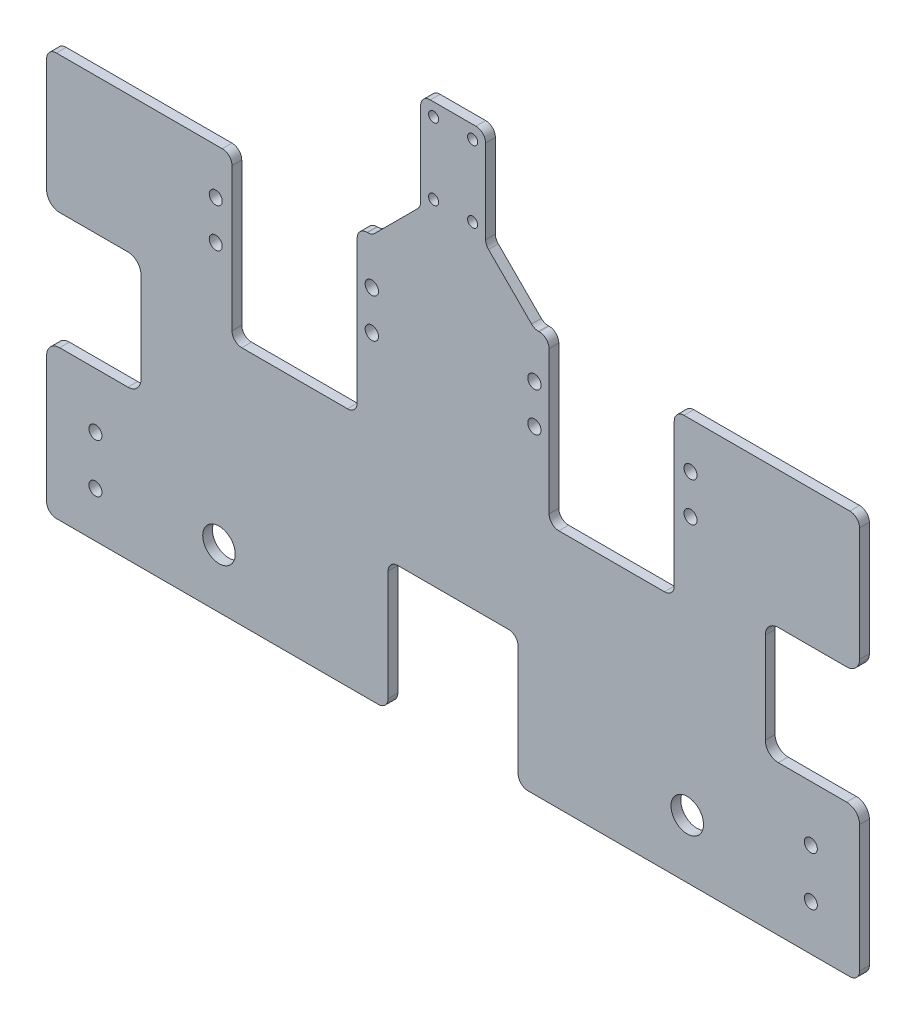
SolidWorks part; units mm, degrees
material "Thornel Mat VMA"
ref_plane "前视基准面" through (0, 0, 0) normal (0, 0, 1) x (1, 0, 0)
ref_plane "上视基准面" through (0, 0, 0) normal (0, 1, 0) x (1, 0, 0)
ref_plane "右视基准面" through (0, 0, 0) normal (1, 0, 0) x (0, 0, -1)
other "Configuration Table"
sketch "草图1" plane through (0, 0, 0) normal (0, 0, 1) x (1, 0, 0)
  line L0 (-32.5, 40) -> (-25, 40)
  line L1 (-25, 40) -> (-10, 55)
  line L2 (-10, 55) -> (-10, 85)
  line L3 (-10, 85) -> (10, 85)
  line L4 (-32.5, 40) -> (-32.5, 0)
  line L5 (-32.5, 0) -> (32.5, 0)
  line L6 (0, 0) -> (0, 50.9699) construction
  line L7 (32.5, 40) -> (32.5, 0)
  line L8 (10, 55) -> (10, 85)
  line L9 (25, 40) -> (10, 55)
  line L10 (32.5, 40) -> (25, 40)
  dimension "D1" = 65
  dimension "D2" = 85
  dimension "D3" = 30
  dimension "D4" = 40
  dimension "D5" = 50
  dimension "D6" = 20
extrude "凸台-拉伸1" add sketch "草图1" along normal blind 3
sketch "草图2" plane through (0, 0, 3) normal (0, 0, 1) x (1, 0, 0)
  line L0 (0, 85) -> (0, 65.679) construction
  line L1 (10, 85) -> (-10, 85) construction
  line L2 (-10, 70) -> (13.1812, 70) construction
  line L3 (-10, 85) -> (-10, 55) construction
  circle A0 centre (-6, 81) radius 1.55
  circle A2 centre (-6, 59) radius 1.55
  circle A3 centre (6, 59) radius 1.55
  circle A4 centre (6, 81) radius 1.55
  dimension "D1" = 4
  dimension "D2" = 4
  dimension "D3" = 3.1
extrude "切除-拉伸1" cut sketch "草图2" against normal through all
sketch "草图3" plane through (0, 0, 3) normal (0, 0, 1) x (1, 0, 0)
  line L0 (32.5, 20) -> (-48.6379, 20) construction
  line L1 (32.5, 0) -> (32.5, 40) construction
  line L2 (0, 0) -> (0, 100.1432) construction
  circle A0 centre (-25, 26) radius 2.05
  circle A2 centre (-25, 14) radius 2.05
  circle A3 centre (25, 14) radius 2.05
  circle A4 centre (25, 26) radius 2.05
  dimension "D1" = 12
  dimension "D2" = 50
  dimension "D3" = 4.1
extrude "切除-拉伸2" cut sketch "草图3" against normal through all
sketch "草图4" plane through (0, 0, 3) normal (0, 0, 1) x (1, 0, 0)
  line L0 (32.5, 0) -> (32.5, 40) construction
  line L1 (32.5, 40) -> (29.5, 40)
  line L2 (32.5, 40) -> (32.5, -0.4765)
  line L3 (32.5, -0.4765) -> (29.5, -0.4765)
  line L4 (29.5, 40) -> (29.5, -0.4765)
  line L5 (0, 85) -> (0, -21.7177) construction
  line L6 (10, 85) -> (-10, 85) construction
  line L7 (-29.5, 40) -> (-29.5, -0.4765)
  line L8 (-32.5, -0.4765) -> (-29.5, -0.4765)
  line L9 (-32.5, 40) -> (-32.5, -0.4765)
  line L10 (-32.5, 40) -> (-29.5, 40)
  dimension "D1" = 3
extrude "切除-拉伸3" cut sketch "草图4" against normal blind 10
sketch "草图5" plane through (0, 0, 3) normal (0, 0, 1) x (1, 0, 0)
  line L0 (0, 0) -> (0, -185.4243) construction
  line L1 (-125, -10) -> (125, -10)
  line L2 (0, 0) -> (0, -84)
  line L3 (-125, -84) -> (125, -84)
  line L4 (125, -10) -> (125, -84)
  line L5 (-125, -10) -> (-125, -84)
  line L6 (-68, -10) -> (-68, 40)
  line L7 (125, -10) -> (68, -10)
  line L8 (125, -10) -> (125, 40)
  line L9 (125, 40) -> (68, 40)
  line L10 (68, -10) -> (68, 40)
  line L11 (-125, 40) -> (-68, 40)
  line L12 (-125, -10) -> (-125, 40)
  line L13 (-125, -10) -> (-68, -10)
  line L14 (-125, -10) -> (-125, -84)
  line L16 (29.5, 40) -> (29.5, 0) construction
  line L17 (-29.5, 0) -> (29.5, 0)
  line L18 (-29.5, 0) -> (-29.5, -10)
  line L19 (-29.5, -10) -> (29.5, -10)
  line L20 (29.5, 0) -> (29.5, -10)
  line M16 (-29.5, 0) -> (29.5, 0)
  dimension "D1" = 250
  dimension "D2" = 50
  dimension "D3" = 68
  dimension "D4" = 74
  dimension "D5" = 10
extrude "凸台-拉伸2" add sketch "草图5" against normal blind 3 contours L10 L1 L8 L9 | L4 L1 L2 L3 | L1 L5 L3 L2 M16 | L12 L1 L6 L11 | L18 L1 L2 M16 | L20 L2 L1 M16 region at (-96.5, 15, 3) region at (-62.5, -47, 3) region at (-14.75, -5, 3) region at (62.5, -47, 3) region at (14.75, -5, 3) region at (96.5, 15, 3)
sketch "草图6" plane through (0, 0, 3) normal (0, 0, 1) x (1, 0, 0)
  line L0 (0, 0) -> (0, -103.0936) construction
  line L1 (-125, -84) -> (125, -84) construction
  line L2 (-20, -84) -> (20, -84)
  line L3 (0, -84) -> (0, -44)
  line L4 (-20, -44) -> (20, -44)
  line L5 (20, -84) -> (20, -44)
  line L6 (-20, -84) -> (-20, -44)
  line M14 (-125, -84) -> (125, -84)
  dimension "D1" = 20
  dimension "D2" = 40
extrude "切除-拉伸4" cut sketch "草图6" against normal blind 4 contours L2 L5 L4 L3 | L6 L3 L4 M14 region at (-10, -64, 3) region at (10, -64, 3)
fillet "圆角1" radius 3 22 edges at (-20, -44, 1.5) (20, -44, 1.5) (20, -84, 1.5) (125, -84, 1.5) (68, 40, 1.5) (68, -10, 1.5) (29.5, -10, 1.5) (29.5, 40, 1.5) (25, 40, 1.5) (10, 55, 1.5) (10, 85, 1.5) (-10, 85, 1.5) (-10, 55, 1.5) (-25, 40, 1.5) (-29.5, 40, 1.5) (-29.5, -10, 1.5) (-68, -10, 1.5) (-68, 40, 1.5) (-125, 40, 1.5) (-125, -84, 1.5) (-20, -84, 1.5) (125, 40, 1.5)
sketch "草图7" plane through (0, 0, 3) normal (0, 0, 1) x (1, 0, 0)
  line L0 (125, -81) -> (125, 37) construction
  line L1 (23, -84) -> (122, -84) construction
  line L2 (0, 0) -> (0, -96.374) construction
  line L3 (122, 40) -> (71, 40) construction
  line L4 (96, -2) -> (127, -2)
  line L5 (96, -2) -> (96, -38)
  line L6 (96, -38) -> (127, -38)
  line L7 (127, -2) -> (127, -38)
  line L8 (-127, -2) -> (-127, -38)
  line L9 (-96, -38) -> (-127, -38)
  line L10 (-96, -2) -> (-96, -38)
  line L11 (-96, -2) -> (-127, -2)
  circle A0 centre (72, -66) radius 5
  circle A1 centre (-72, -66) radius 5
  dimension "D1" = 53
  dimension "D2" = 10
  dimension "D3" = 18
  dimension "D4" = 42
  dimension "D5" = 29
  dimension "D6" = 36
  dimension "D7" = 31
extrude "切除-拉伸5" cut sketch "草图7" against normal blind 4
sketch "草图8" plane through (0, 0, 3) normal (0, 0, 1) x (1, 0, 0)
  line L0 (0, 95.4541) -> (0, -92.5342) construction
  line L1 (122, 40) -> (71, 40) construction
  line L2 (125, -2) -> (125, 37) construction
  circle A0 centre (73, 26) radius 2
  circle A1 centre (73, 14) radius 2
  circle A2 centre (-73, 14) radius 2
  circle A3 centre (-73, 26) radius 2
  dimension "D1" = 4
  dimension "D2" = 4
  dimension "D3" = 12
  dimension "D4" = 14
  dimension "D5" = 52
  dimension "D6" = 52
extrude "切除-拉伸6" cut sketch "草图8" against normal blind 4
sketch "草图9" plane through (0, 0, 3) normal (0, 0, 1) x (1, 0, 0)
  line L1 (125, -81) -> (125, -38) construction
  line L2 (0, 116.3395) -> (0, -160.2335) construction
  line L3 (23, -84) -> (122, -84) construction
  circle A0 centre (110, -55) radius 2
  circle A1 centre (110, -70) radius 2
  circle A2 centre (-110, -70) radius 2
  circle A3 centre (-110, -55) radius 2
  dimension "D1" = 4
  dimension "D2" = 4
  dimension "D3" = 15
  dimension "D4" = 14
  dimension "D5" = 15
  dimension "D6" = 15
extrude "切除-拉伸7" cut sketch "草图9" against normal blind 4
fillet "圆角2" radius 4 8 edges at (-96, -38, 1.5) (-125, -38, 1.5) (125, -38, 1.5) (96, -38, 1.5) (125, -2, 1.5) (-125, -2, 1.5) (-96, -2, 1.5) (96, -2, 1.5)
